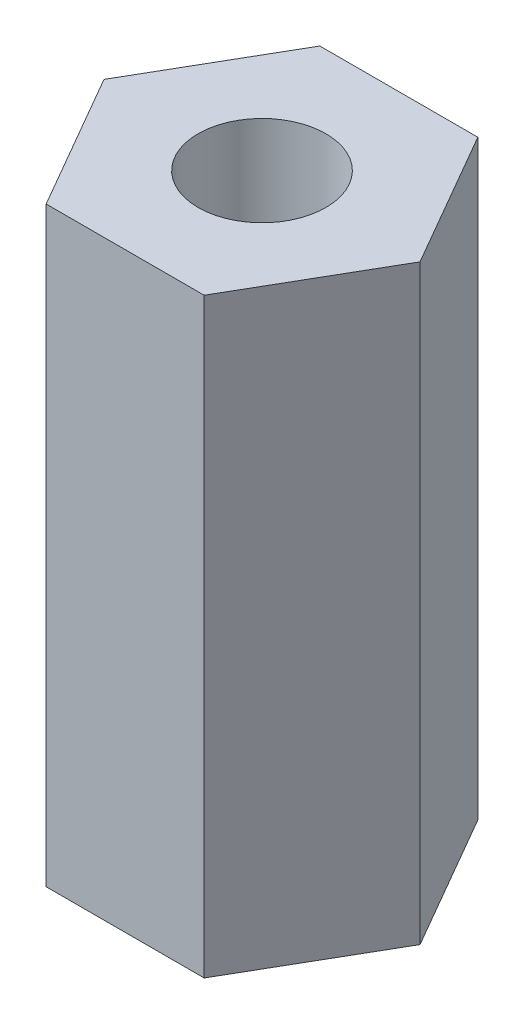
SolidWorks part; units mm, degrees
ref_plane "Front Plane" through (0, 0, 0) normal (0, 0, 1) x (1, 0, 0)
ref_plane "Top Plane" through (0, 0, 0) normal (0, 1, 0) x (1, 0, 0)
ref_plane "Right Plane" through (0, 0, 0) normal (1, 0, 0) x (0, 0, -1)
sketch "Croquis1" plane through (0, 0, 0) normal (0, 1, 0) x (1, 0, 0)
  line L1 (1.9774, -3.425) -> (3.9548, 0)
  line L2 (3.9548, 0) -> (1.9774, 3.425)
  line L3 (1.9774, 3.425) -> (-1.9774, 3.425)
  line L4 (-1.9774, 3.425) -> (-3.9548, 0)
  line L5 (-3.9548, 0) -> (-1.9774, -3.425)
  line L6 (-1.9774, -3.425) -> (1.9774, -3.425)
  line L7 (1.4001, -2.425) -> (2.8001, 0)
  line L8 (2.8001, 0) -> (1.4001, 2.425)
  line L9 (1.4001, 2.425) -> (-1.4001, 2.425)
  line L10 (-1.4001, 2.425) -> (-2.8001, 0)
  line L11 (-2.8001, 0) -> (-1.4001, -2.425)
  line L12 (-1.4001, -2.425) -> (1.4001, -2.425)
  circle A0 centre (0, 0) radius 3.425 construction
  circle A1 centre (0, 0) radius 2.425 construction
  dimension "D1" = 1
  dimension "D2" = 4.85
extrude "Saliente-Extruir1" add sketch "Croquis1" along normal blind 14.8 contours L1 L2 L3 L4 L5 L6
extrude "Cortar-Extruir1" cut sketch "Croquis1<3>" along normal blind 10.05 contours L11 L12 L7 L8 L9 L10 region at (0, 0, 0)
sketch "Croquis1<3>" plane through (0, 0, 0) normal (0, 1, 0) x (1, 0, 0) same geometry as "Croquis1"
sketch "Croquis2" plane through (0, 14.8, 0) normal (0, 1, 0) x (1, 0, 0)
  circle A0 centre (0, 0) radius 1.6
  dimension "D1" = 3.2
extrude "Cortar-Extruir2" cut sketch "Croquis2" against normal blind 5
